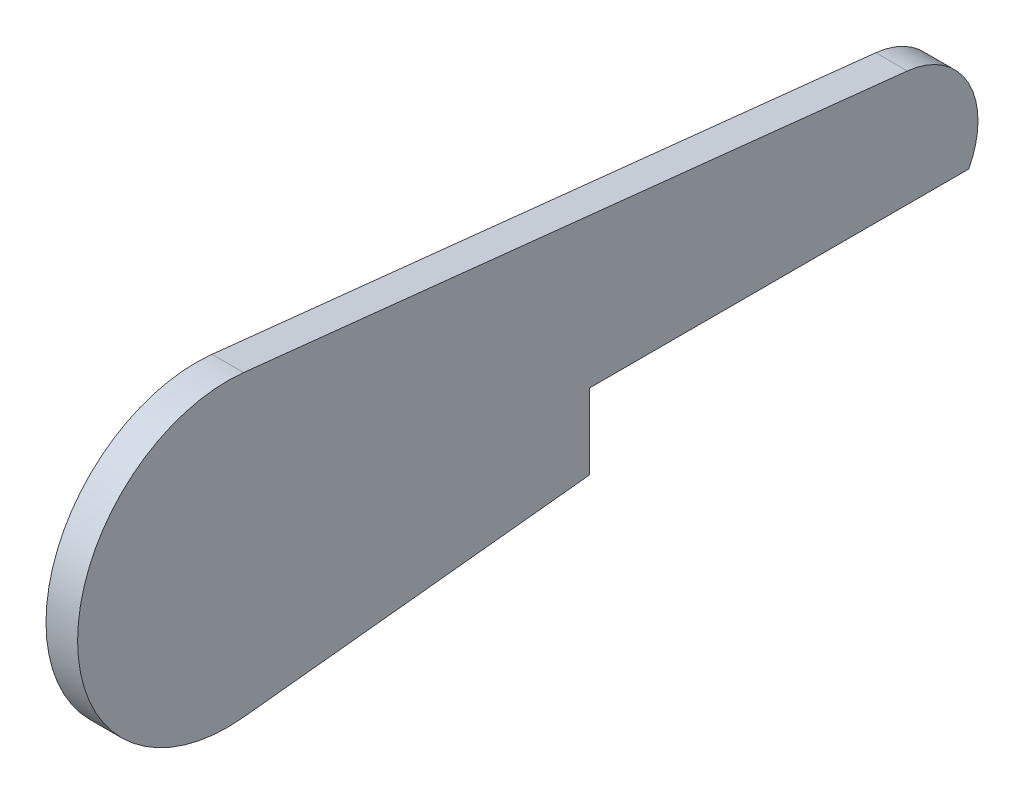
SolidWorks part; units mm, degrees
ref_plane "Płaszczyzna przednia" through (0, 0, 0) normal (0, 0, 1) x (1, 0, 0)
ref_plane "Płaszczyzna górna" through (0, 0, 0) normal (0, 1, 0) x (1, 0, 0)
ref_plane "Płaszczyzna prawa" through (0, 0, 0) normal (1, 0, 0) x (0, 0, -1)
sketch "Szkic1" plane through (0, 0, 0) normal (1, 0, 0) x (0, 0, -1)
  line L0 (0, 0) -> (240, 0) construction
  line L1 (10.0588, 94.466) -> (430.2941, 49.7189)
  line L2 (430.2941, -49.7189) -> (10.0588, -94.466)
  arc A0 (10.0588, 94.466) -> (10.0588, -94.466) centre (0, 0) ccw
  arc A1 (430.2941, -49.7189) -> (430.2941, 49.7189) centre (425, 0) ccw
  dimension "D1" = 425
  dimension "D2" = 190
  dimension "D3" = 100
extrude "Dodanie-wyciągnięcie1" add sketch "Szkic1" along normal blind 5
sketch "Szkic2" plane through (0, 0, 0) normal (-1, 0, 0) x (0, 0, 1)
  line L0 (-9.5294, 89.4941) -> (-429.7647, 44.747)
  line L1 (-429.7647, -44.747) -> (-9.5294, -89.4941)
  line L2 (-10.0588, 94.466) -> (-430.2941, 49.7189)
  line L3 (-430.2941, -49.7189) -> (-10.0588, -94.466)
  line L4 (-10.0588, 94.466) -> (-430.2941, 49.7189)
  line L5 (-430.2941, -49.7189) -> (-10.0588, -94.466)
  arc A0 (-9.5294, -89.4941) -> (-9.5294, 89.4941) centre (0, 0) ccw
  arc A1 (-429.7647, 44.747) -> (-429.7647, -44.747) centre (-425, 0) ccw
  arc A2 (-10.0588, -94.466) -> (-10.0588, 94.466) centre (0, 0) ccw
  arc A3 (-430.2941, 49.7189) -> (-430.2941, -49.7189) centre (-425, 0) ccw
  arc A4 (-10.0588, -94.466) -> (-10.0588, 94.466) centre (0, 0) ccw
  arc A5 (-430.2941, 49.7189) -> (-430.2941, -49.7189) centre (-425, 0) ccw
  dimension "D1" = 0
  dimension "D2" = 5
extrude "Dodanie-wyciągnięcie2" add sketch "Szkic2" along normal blind 15
sketch "Szkic3" plane through (0, 0, 0) normal (-1, 0, 0) x (0, 0, 1)
  circle A0 centre (-425, 0) radius 10.5608
  circle A1 centre (0, 0) radius 15.5726
  point P6 (-240, 0)
  point P7 (0, 0)
extrude "Dodanie-wyciągnięcie3" add sketch "Szkic3" along normal blind 2
sketch "Szkic4" plane through (5, 0, 0) normal (1, 0, 0) x (0, 0, -1)
  line L0 (469.1312, -23.5039) -> (229.0845, -23.5039)
  line L3 (229.0845, -71.1439) -> (435.2326, -49.7254)
  line L5 (229.0845, -23.5039) -> (229.0845, -71.1439)
  line L6 (10.0588, -94.466) -> (430.2941, -49.7189)
  line L7 (430.2941, 49.7189) -> (10.0588, 94.466)
  line L8 (229.0845, -71.1439) -> (430.2941, -49.7189)
  arc A0 (430.2941, -49.7189) -> (430.2941, 49.7189) centre (425, 0) ccw construction
  arc A3 (10.0588, 94.466) -> (10.0588, -94.466) centre (0, 0) ccw
  arc A4 (430.2941, -49.7189) -> (430.2941, 49.7189) centre (425, 0) ccw
  arc A6 (430.2941, -49.7189) -> (469.1312, -23.5039) centre (425, 0) ccw
  line M6 (10.0588, -94.466) -> (430.2941, -49.7189)
  arc M7 (430.2941, -49.7189) -> (430.2941, 49.7189) centre (425, 0) ccw
  dimension "D1" = 0
extrude "Wytnij-wyciągnięcie1" cut sketch "Szkic4" against normal blind 20 contours L0 M6 M7 region at (5, -41.7545, -330.6597)
